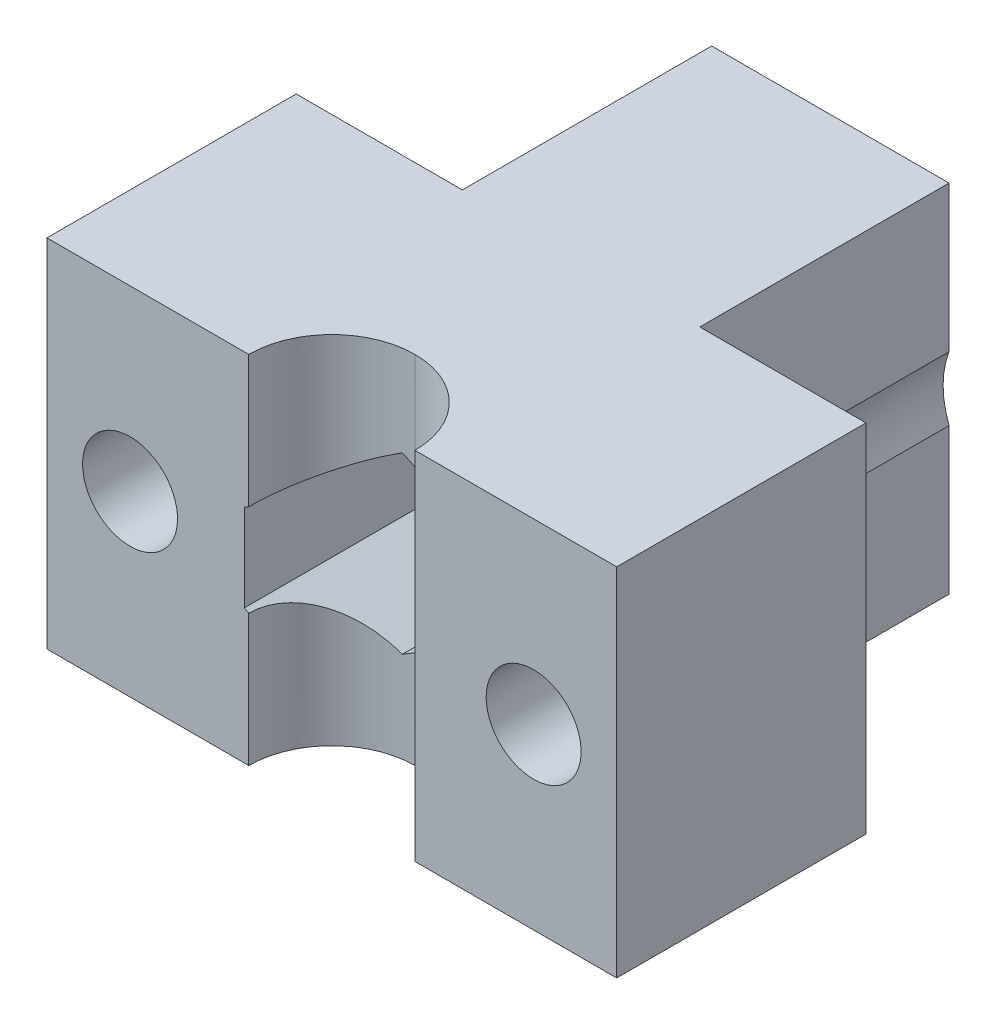
SolidWorks part; units mm, degrees
ref_plane "Спереди" through (0, 0, 0) normal (0, 0, 1) x (1, 0, 0)
ref_plane "Сверху" through (0, 0, 0) normal (0, 1, 0) x (1, 0, 0)
ref_plane "Справа" through (0, 0, 0) normal (1, 0, 0) x (0, 0, -1)
sketch "Эскиз1" plane through (0, 0, 0) normal (0, 1, 0) x (1, 0, 0)
  line L1 (-24, -10) -> (24, -10)
  line L2 (-24, -10) -> (-24, 10)
  line L3 (-24, 10) -> (24, 10)
  line L4 (24, -10) -> (24, 10)
  line L5 (-24, -10) -> (24, 10) construction
  line L6 (-24, 10) -> (24, -10) construction
  point P0 (0, 0)
  dimension "D1" = 48
  dimension "D2" = 20
extrude "Бобышка-Вытянуть1" add sketch "Эскиз1" along normal blind 30
sketch "Эскиз2" plane through (0, 0, 10) normal (0, 0, 1) x (1, 0, 0)
  line L0 (-7, 30) -> (-7, 0)
  line L1 (-24, 30) -> (24, 30) construction
  line L2 (-24, 0) -> (24, 0) construction
  line L3 (-7, 0) -> (7, 0)
  line L4 (7, 0) -> (7, 30)
  line L5 (7, 30) -> (-7, 30)
  dimension "D1" = 17
  dimension "D2" = 14
extrude "Вырез-Вытянуть1" cut sketch "Эскиз2" against normal blind 7
sketch "Эскиз7" plane through (24, 0, 0) normal (1, 0, 0) x (0, 0, -1)
  line L1 (32, 30) -> (32, 0)
  line L2 (32, 0) -> (10, 0)
  line L3 (-10, 0) -> (10, 0)
  line L4 (10, 0) -> (10.066, 0.2736)
  line L5 (10, 30) -> (32, 30)
  line L8 (10, 0) -> (10, 30)
  dimension "D3" = 22
extrude "Бобышка-Вытянуть2" add sketch "Эскиз7" against normal blind 48
sketch "Эскиз8" plane through (24, 0, 0) normal (1, 0, 0) x (0, 0, -1)
  line L0 (11, 0) -> (11, 30)
  line L1 (-10, 30) -> (32, 30) construction
  line L2 (11, 30) -> (32, 30)
  line L3 (11, 0) -> (32, 0)
  line L4 (32, 0) -> (32, 30)
  line L5 (-10, 0) -> (32, 0) construction
  point P16 (11, 0)
extrude "Вырез-Вытянуть2" cut sketch "Эскиз8" against normal blind 14
sketch "Эскиз9" plane through (-24, 0, 0) normal (-1, 0, 0) x (0, 0, 1)
  line L0 (-11, 0) -> (-11, 30)
  line L1 (-32, 30) -> (10, 30) construction
  line L2 (-11, 30) -> (-32, 30)
  line L3 (-32, 0) -> (10, 0) construction
  line L4 (-11, 0) -> (-32, 0)
  line L5 (-32, 0) -> (-32, 30)
  point P15 (-11, 0)
extrude "Вырез-Вытянуть3" cut sketch "Эскиз9" against normal blind 14
sketch "Эскиз11" plane through (-10, 0, 0) normal (-1, 0, 0) x (0, 0, 1)
  line L0 (-32, 30) -> (-11, 0) construction
  line L2 (-32, 0) -> (-11, 0) construction
  line L3 (-16.3, 4.8) -> (-16.3, 25.2)
  line L6 (-16.3, 4.8) -> (-26.7, 4.8)
  line L7 (-16.3, 25.2) -> (-26.7, 25.2)
  line L8 (-26.7, 4.8) -> (-26.7, 25.2)
  line L9 (-16.3, 4.8) -> (-26.7, 25.2) construction
  line L10 (-16.3, 25.2) -> (-26.7, 4.8) construction
  point P7 (-21.5, 15)
  point P8 (-21.5, 15)
  dimension "D1" = 20.4
  dimension "D2" = 10.4
extrude "Вырез-Вытянуть4" cut sketch "Эскиз11" against normal through all
sketch "Эскиз13" plane through (0, 0, -11) normal (0, 0, -1) x (-1, 0, 0)
  line L0 (24, 15) -> (10, 15) construction
  line L1 (24, 0) -> (24, 30) construction
  line L2 (10, 0) -> (10, 30) construction
  circle A0 centre (17, 15) radius 4
extrude "Вырез-Вытянуть5" cut sketch "Эскиз13" against normal through all
sketch "Эскиз14" plane through (0, 0, -11) normal (0, 0, -1) x (-1, 0, 0)
  line L0 (-24, 15) -> (-10, 15) construction
  line L1 (-24, 30) -> (-24, 0) construction
  line L2 (-10, 30) -> (-10, 0) construction
  circle A0 centre (-17, 15) radius 4
extrude "Вырез-Вытянуть6" cut sketch "Эскиз14" against normal through all
fillet "Скругление1" radius 7 2 edges at (-7, 15, 3) (7, 15, 3)
sketch "Sketch1" plane through (10, 0, 0) normal (1, 0, 0) x (0, 0, -1)
  line L0 (16.3, 25.2) -> (26.7, 4.8) construction
  line L2 (26.7, 4.8) -> (16.3, 4.8)
  line L3 (26.7, 4.8) -> (26.7, 25.2)
  line L4 (26.7, 25.2) -> (16.3, 25.2)
  line L5 (16.3, 4.8) -> (16.3, 25.2)
  line L6 (26.7, 4.8) -> (16.3, 25.2) construction
  line L7 (26.7, 25.2) -> (16.3, 4.8) construction
  point P4 (21.5, 15)
extrude "Boss-Extrude1" add sketch "Sketch1" against normal blind 4
sketch "Эскиз20" plane through (0, 0, -11) normal (0, 0, -1) x (-1, 0, 0)
  circle A0 centre (-17, 15) radius 7.5
  circle A1 centre (17, 15) radius 7.5
  dimension "D1" = 15
extrude "Вырез-Вытянуть8" cut sketch "Эскиз20" along normal through all
sketch "Sketch3" plane through (0, 0, -32) normal (0, 0, -1) x (-1, 0, 0)
  line L0 (1, 30) -> (1, 0) construction
  line L1 (10, 30) -> (-10, 30) construction
  line L2 (10, 0) -> (-10, 0) construction
  circle A0 centre (1, 15) radius 4
  dimension "D1" = 8
  dimension "D2" = 9
extrude "Cut-Extrude2" cut sketch "Sketch3" against normal through all
sketch "Sketch4" plane through (0, 0, -32) normal (0, 0, -1) x (-1, 0, 0)
  line L1 (1, 22.35) -> (-5.3653, 18.675)
  line L2 (-5.3653, 18.675) -> (-5.3653, 11.325)
  line L3 (-5.3653, 11.325) -> (1, 7.65)
  line L4 (1, 7.65) -> (7.3653, 11.325)
  line L5 (7.3653, 11.325) -> (7.3653, 18.675)
  line L6 (7.3653, 18.675) -> (1, 22.35)
  circle A0 centre (1, 15) radius 7.35 construction
extrude "Cut-Extrude3" cut sketch "Sketch4" against normal blind 20 from offset 25 offset against normal yes
